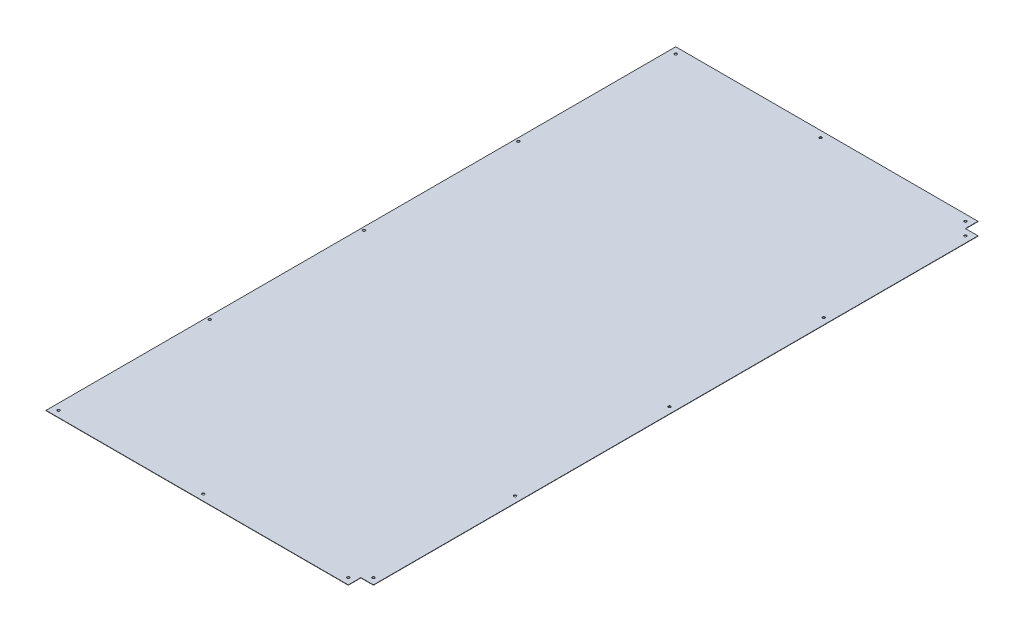
SolidWorks part; units mm, degrees
ref_plane "Front Plane" through (0, 0, 0) normal (0, 0, 1) x (1, 0, 0)
ref_plane "Top Plane" through (0, 0, 0) normal (0, 1, 0) x (1, 0, 0)
ref_plane "Right Plane" through (0, 0, 0) normal (1, 0, 0) x (0, 0, -1)
sketch "Sketch1" plane through (0, 0, 0) normal (0, 1, 0) x (1, 0, 0)
  line L28 (-500, 1000) -> (460, 1000)
  line L37 (-500, 1000) -> (-500, -1000)
  line L38 (-500, -1000) -> (460, -1000)
  line L42 (500, -960) -> (460, -960)
  line L43 (460, -1000) -> (460, -960)
  line L46 (500, 960) -> (460, 960)
  line L47 (460, 1000) -> (460, 960)
  line L62 (500, -960) -> (500, 960)
  circle A0 centre (480, 940) radius 3
  circle A1 centre (440, 980) radius 3
  circle A2 centre (480, -940) radius 3
  circle A3 centre (440, -980) radius 3
  circle A4 centre (-490, 0) radius 3
  circle A7 centre (-20, 980) radius 3
  circle A8 centre (-20, -980) radius 3
  circle A13 centre (480, 490) radius 3
  circle A14 centre (-480, -980) radius 3
  circle A15 centre (-480, 980) radius 3
  circle A18 centre (-490, 490) radius 3
  circle A19 centre (-500, 490) radius 3 [skipped]
  circle A20 centre (-500, 0) radius 3 [skipped]
  circle A24 centre (-490, -490) radius 3
  circle A25 centre (480, -490) radius 3
  circle A26 centre (480, 0) radius 3
  point P0 (0, 0)
  dimension "D3" = 460
  dimension "D1" = 6
  dimension "D2" = 6
  dimension "D13" = 6
  dimension "D9" = 6
  dimension "D4" = 460
  dimension "D5" = 20
  dimension "D6" = 20
  dimension "D7" = 1000
  dimension "D8" = 40
  dimension "D10" = 2
  dimension "D11" = 2000
  dimension "D12" = 2
  dimension "D14" = 10
  dimension "D15" = 10
  dimension "D16" = 10
extrude "Boss-Extrude1" add sketch "Sketch1" along normal blind 1 contours L42 L62 L46 L47 L28 L37 L38 L43 A26 A24 A18 A15 A14 A13 A8 A7 A4 A3 A2 A1 A0 A25
chamfer "Chamfer1" distance 1 angle 45 14 edges at (-20, 1, 983) (-490, 1, 3) (-20, 1, -977) (440, 1, -977) (480, 1, -937) (480, 1, -487) (480, 1, 943) (440, 1, 983) (-480, 1, -977) (-480, 1, 983) (-490, 1, -487) (-490, 1, 493) (480, 1, 3) (480, 1, 493)
